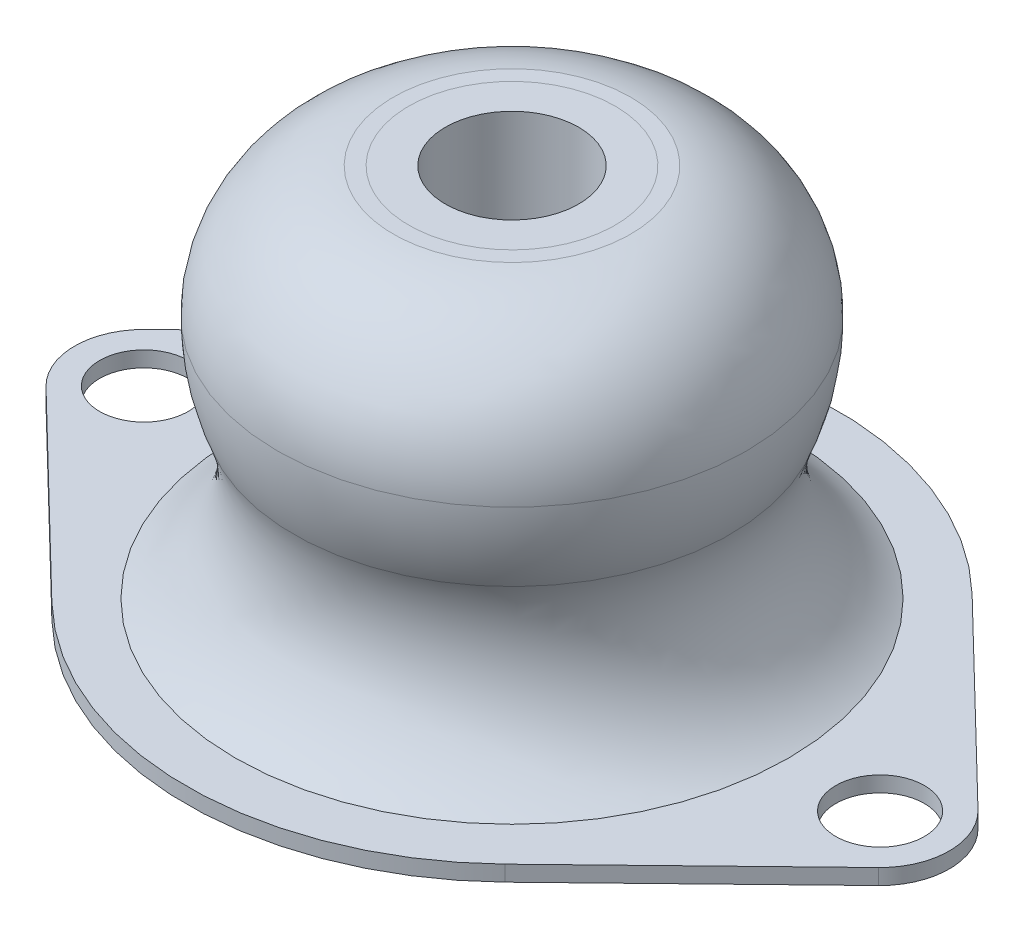
SolidWorks part; units mm, degrees
ref_plane "Front Plane" through (0, 0, 0) normal (0, 0, 1) x (1, 0, 0)
ref_plane "Top Plane" through (0, 0, 0) normal (0, 1, 0) x (1, 0, 0)
ref_plane "Right Plane" through (0, 0, 0) normal (1, 0, 0) x (0, 0, -1)
sketch "Sketch1" plane through (0, 0, 0) normal (0, 0, 1) x (1, 0, 0)
  line L0 (0, -9.525) -> (0, 9.525) construction
  line L1 (-21.336, -9.525) -> (21.336, -9.525) construction
  line L2 (-11.43, 9.525) -> (11.43, 9.525) construction
  line L3 (-3.2512, 3.175) -> (3.2512, 3.175) construction
  line L4 (-21.336, -9.525) -> (-21.336, -8.763) construction
  line L5 (-21.336, -8.763) -> (21.336, -8.763) construction
  line L6 (21.336, -8.763) -> (21.336, -9.525) construction
  line L7 (-17.9578, -9.525) -> (-17.9578, -8.763) construction
  line L8 (17.9578, -9.525) -> (17.9578, -8.763) construction
  line L9 (-11.43, 9.525) -> (-11.43, -8.763) construction
  line L10 (-5.7912, 9.525) -> (-3.2512, 9.525)
  line L11 (-8.255, -3.175) -> (8.255, -3.175) construction
  line L12 (-21.1836, -3.175) -> (-21.1836, -9.525) construction
  line L13 (-21.1836, -3.175) -> (-21.1836, 3.175) construction
  line L16 (-11.43, 3.175) -> (-3.2512, 3.175) construction
  line L18 (-3.2512, 3.175) -> (-3.2512, 9.525)
  line L19 (-5.0351, 3.175) -> (-5.0351, 9.525)
  line L23 (-9.525, -9.525) -> (-9.525, -8.763) construction
  line L24 (-13.4937, -8.763) -> (-9.525, -8.763)
  line L28 (-6.9239, 3.175) -> (-5.0351, 3.175)
  arc A0 (-5.7912, 9.525) -> (-11.43, 3.175) centre (-5.0351, 3.175) ccw
  arc A3 (-11.43, 3.175) -> (-10.6485, -0.7326) centre (-1.2702, 3.175) ccw
  arc A5 (-9.525, -8.763) -> (-8.8214, 0.6097) centre (-21.1836, -3.175) ccw
  arc A8 (-6.9239, 3.175) -> (-8.8214, 0.6097) centre (-6.9239, 1.1906) ccw
  arc A10 (-13.4937, -8.763) -> (-10.6485, -0.7326) centre (-16.5102, -3.175) ccw
  point P5 (-9.525, -9.525)
  point P6 (9.525, -9.525)
  point P7 (0, 9.525)
  point P11 (0, 3.175)
  point P19 (-15.7988, -8.763)
  point P20 (-20.1168, -8.763)
  point P21 (15.875, -9.525)
  point P22 (-15.875, -9.525)
  point P27 (0, -3.175)
  point P42 (-13.4937, -8.763)
  point P53 (-10.16, -3.175)
  dimension "R" = 1.9844
  dimension "Base Length" = 42.672
  dimension "Overall Height" = 19.05
  dimension "Bottom Diameter" = 19.05
  dimension "Diameter" = 22.86
  dimension "Hole Diameter" = 6.5024
  dimension "Hole Depth" = 6.35
  dimension "Base Height" = 0.762
  dimension "Mounting Hole Spacing" = 35.9156
  dimension "Mounting Hole Diameter" = 4.318
  dimension "Base Width" = 31.75
  dimension "Minor Internal ID" = 16.51
  dimension "D1" = 2.54
  dimension "Bottom Rubber Diameter" = 26.9875
  dimension "D2" = 1.27
sketch "Sketch2" plane through (0, 0, 0) normal (0, 0, 1) x (1, 0, 0)
  line L0 (-13.4938, -8.763) -> (-9.525, -8.763) construction
  line L1 (-6.9239, 3.175) -> (-5.0351, 3.175) construction
  line L2 (-13.4938, -8.763) -> (-9.525, -8.763)
  line L3 (-6.9239, 3.175) -> (-5.0351, 3.175)
  line L4 (-5.0351, 3.175) -> (-5.0351, 9.525) construction
  line L5 (-5.0351, 3.175) -> (-5.0351, 9.525)
  line L6 (-5.7912, 9.525) -> (-3.2512, 9.525) construction
  line L7 (-5.7912, 9.525) -> (-5.0351, 9.525)
  line L8 (0, -9.525) -> (0, 9.525) construction
  line L9 (0, -9.525) -> (0, 9.525) construction
  line L10 (5.7912, 9.525) -> (5.0351, 9.525) construction
  line L11 (5.0351, 3.175) -> (5.0351, 9.525) construction
  line L12 (6.9239, 3.175) -> (5.0351, 3.175) construction
  line L13 (13.4938, -8.763) -> (9.525, -8.763) construction
  line L14 (3.2512, 9.525) -> (3.2512, 3.175) construction
  line L15 (-3.2512, 9.525) -> (0, 9.525) construction
  line L16 (0, 9.525) -> (3.2512, 9.525) construction
  arc A0 (-9.525, -8.763) -> (-8.8214, 0.6097) centre (-21.1836, -3.175) ccw construction
  arc A1 (-13.4938, -8.763) -> (-10.6485, -0.7326) centre (-16.5102, -3.175) ccw construction
  arc A2 (-11.43, 3.175) -> (-10.6485, -0.7326) centre (-1.2702, 3.175) ccw construction
  arc A3 (-6.9239, 3.175) -> (-8.8214, 0.6097) centre (-6.9239, 1.1906) ccw construction
  arc A4 (-5.7912, 9.525) -> (-11.43, 3.175) centre (-5.0351, 3.175) ccw construction
  arc A5 (-9.525, -8.763) -> (-8.8214, 0.6097) centre (-21.1836, -3.175) ccw
  arc A6 (-13.4938, -8.763) -> (-10.6485, -0.7326) centre (-16.5102, -3.175) ccw
  arc A7 (-11.43, 3.175) -> (-10.6485, -0.7326) centre (-1.2702, 3.175) ccw
  arc A8 (-6.9239, 3.175) -> (-8.8214, 0.6097) centre (-6.9239, 1.1906) ccw
  arc A9 (-5.7912, 9.525) -> (-11.43, 3.175) centre (-5.0351, 3.175) ccw
  arc A10 (5.7912, 9.525) -> (11.43, 3.175) centre (5.0351, 3.175) cw construction
  arc A11 (6.9239, 3.175) -> (8.8214, 0.6097) centre (6.9239, 1.1906) cw construction
  arc A12 (11.43, 3.175) -> (10.6485, -0.7326) centre (1.2702, 3.175) cw construction
  arc A13 (13.4938, -8.763) -> (10.6485, -0.7326) centre (16.5102, -3.175) cw construction
  arc A14 (9.525, -8.763) -> (8.8214, 0.6097) centre (21.1836, -3.175) cw construction
revolve "Revolve1" add sketch "Sketch2" angle 360 about L0
sketch "Sketch3" plane through (0, 0, 0) normal (0, 0, 1) x (1, 0, 0)
  line L0 (-11.43, 3.175) -> (-3.2512, 3.175) construction
  line L1 (-3.2512, 3.175) -> (-3.2512, 9.525) construction
  line L2 (-5.7912, 9.525) -> (-3.2512, 9.525) construction
  line L3 (-5.0351, 3.175) -> (-5.0351, 9.525) construction
  line L4 (-5.0351, 3.175) -> (-3.2512, 3.175)
  line L5 (-3.2512, 3.175) -> (-3.2512, 9.525)
  line L6 (-5.0351, 9.525) -> (-3.2512, 9.525)
  line L7 (-5.0351, 3.175) -> (-5.0351, 9.525)
revolve "Revolve2" add sketch "Sketch3" angle 360 about L0
sketch "Sketch4" plane through (0, 0, 0) normal (0, -1, 0) x (1, 0, 0)
  line L0 (-20.3087, -2.426) -> (-11.0474, -11.4005)
  line L1 (-20.3087, 2.426) -> (-11.0474, 11.4005)
  line L2 (20.3087, 2.426) -> (11.0474, 11.4005)
  line L3 (20.3087, -2.426) -> (11.0474, -11.4005)
  line L4 (-21.336, 0) -> (21.336, 0) construction
  arc A0 (11.0474, 11.4005) -> (-11.0474, 11.4005) centre (0, 0) ccw
  circle A1 centre (-17.9578, 0) radius 2.159
  circle A2 centre (17.9578, 0) radius 2.159
  arc A3 (-20.3087, 2.426) -> (-20.3087, -2.426) centre (-17.9578, 0) ccw
  arc A4 (20.3087, -2.426) -> (20.3087, 2.426) centre (17.9578, 0) ccw
  arc A5 (-11.0474, -11.4005) -> (11.0474, -11.4005) centre (0, 0) ccw
  circle A6 centre (0, 0) radius 9.525
  point P1 (0, 15.875)
  point P8 (0, -15.875)
extrude "Boss-Extrude1" add sketch "Sketch4" against normal blind 0.762 from vertex separate body starting at point (-9.525, -9.525, 0)
equation "\"D1@Sketch1\"=\"Diameter@Sketch1\"/9"
equation "\"D2@Sketch1\"=\"Diameter@Sketch1\"/18"
equation "\"D1@Boss-Extrude1\"=\"Base Height@Sketch1\""
